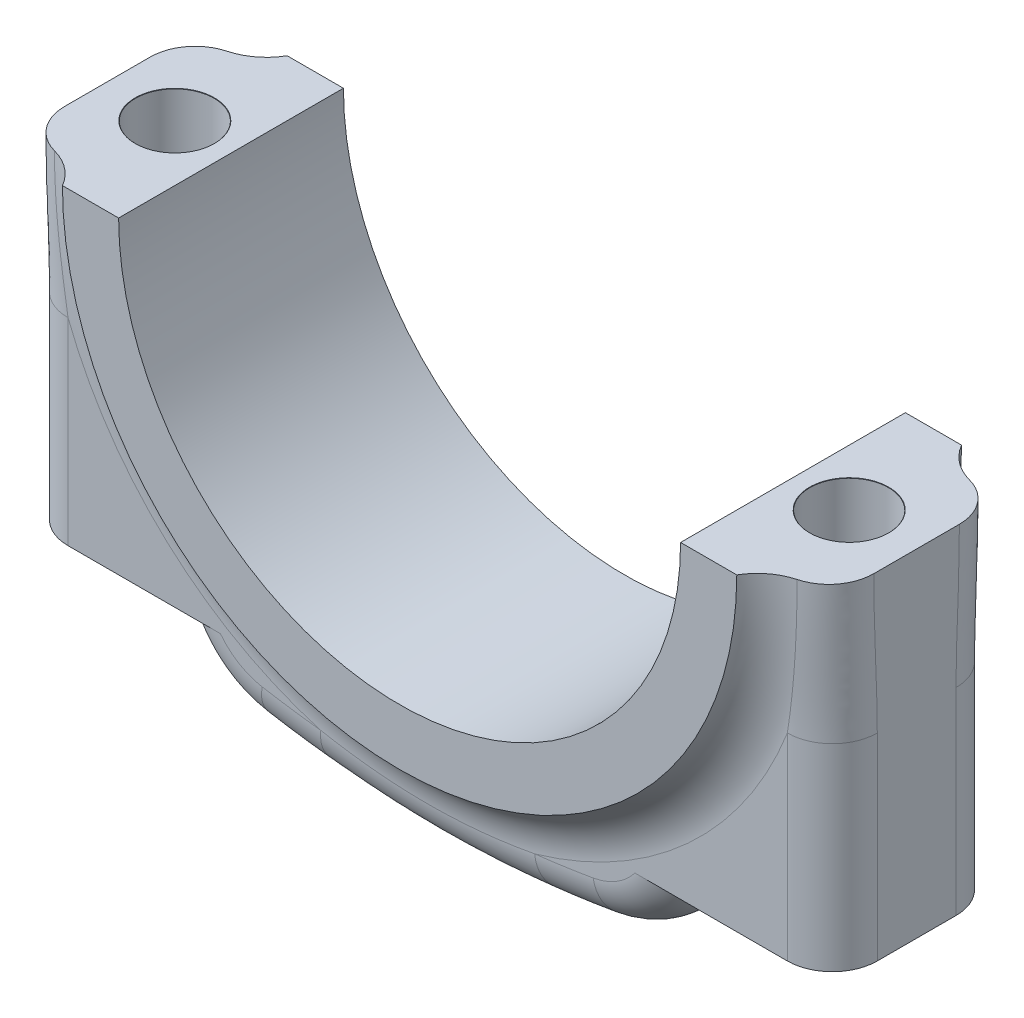
SolidWorks part; units mm, degrees
material "1060 Alloy"
ref_plane "Ebene vorne" through (0, 0, 0) normal (0, 0, 1) x (1, 0, 0)
ref_plane "Ebene oben" through (0, 0, 0) normal (0, 1, 0) x (1, 0, 0)
ref_plane "Ebene rechts" through (0, 0, 0) normal (1, 0, 0) x (0, 0, -1)
sketch "Sketch1" plane through (0, 0, 0) normal (0, 0, 1) x (1, 0, 0)
  line L0 (-36, 0) -> (-25, 0)
  line L1 (36, 0) -> (36, -30)
  line L2 (0, 49.3869) -> (0, -64.5829) construction
  line L3 (-36, 0) -> (-36, -30)
  line L4 (25, 0) -> (36, 0)
  arc A0 (-25, 0) -> (25, 0) centre (0, 0) ccw
  arc A1 (-36, -30) -> (36, -30) centre (0, 52.4864) ccw
  dimension "D3" = 50
  dimension "D4" = 180
  dimension "D1" = 36
  dimension "D2" = 30
extrude "Boss-Extrude1" add sketch "Sketch1" along normal mid plane 15
sketch "Sketch2" plane through (0, 0, 7.5) normal (0, 0, 1) x (1, 0, 0)
  line L0 (-30, 0) -> (-25, 0)
  line L1 (25, 0) -> (30, 0)
  arc A0 (-25, 0) -> (25, 0) centre (0, 0) ccw construction
  arc A1 (-25, 0) -> (25, 0) centre (0, 0) ccw
  arc A2 (-30, 0) -> (30, 0) centre (0, 0) ccw
  dimension "D1" = 60
extrude "Boss-Extrude2" add sketch "Sketch2" along normal blind 2.5
sketch "Sketch3" plane through (0, 0, -7.5) normal (0, 0, -1) x (-1, 0, 0)
  line L2 (30, 0) -> (25, 0)
  line L3 (-25, 0) -> (-30, 0)
  line L4 (30, 0) -> (25, 0)
  line L5 (-25, 0) -> (-30, 0)
  arc A2 (-25, 0) -> (25, 0) centre (0, 0) ccw
  arc A3 (-30, 0) -> (30, 0) centre (0, 0) ccw
  arc A4 (-25, 0) -> (25, 0) centre (0, 0) ccw
  arc A5 (-30, 0) -> (30, 0) centre (0, 0) ccw
  dimension "D1" = 0
extrude "Boss-Extrude3" add sketch "Sketch3" along normal blind 2.5
fillet "Fillet1" radius 5 2 edges at (0, -30, -7.5) (0, -30, 7.5)
hole_wizard "Ø7.0 (7) Diameter Hole5" positions "Sketch4" profile "Sketch5" hole size "Ø7.0" standard "ISO" end condition through all
sketch "Sketch4" plane through (0, 0, 0) normal (0, 1, 0) x (1, 0, 0)
  line L0 (0, 0) -> (0, 15.0556) construction
  point P0 (30, 0)
  point P2 (-30, 0)
  dimension "D1" = 30
sketch "Sketch5" plane through (30, 0, 0) normal (1, 0, 0) x (0, 0, 1)
  line L0 (0, 0) -> (0, 37.5136)
  line L1 (0, 37.5136) -> (3.5, 37.5136)
  line L2 (3.5, 37.5136) -> (3.5, 0.025)
  line L3 (3.5, 0.025) -> (3.525, 0)
  line L5 (3.525, 0) -> (0, 0)
  line L6 (-3.5, 0.025) -> (-3.525, 0) construction
  line L11 (0, -6.35) -> (0, 107.95) construction
  dimension "Thru Hole Dia." = 7
  dimension "Thru Hole Depth" = 37.5136
  dimension "Near C'Sink Dia." = 7.05
  dimension "Near C'Sink Angle" = 90
ref_plane "Plane1" through (0, -30, 0) normal (0, 1, 0) x (1, 0, 0)
sketch "Sketch6" plane through (0, -30, 0) normal (0, 1, 0) x (1, 0, 0)
  line L0 (0, 0.5683) -> (0, -22.8934) construction
  line L1 (23, -13.2327) -> (43.5392, -13.2327)
  line L2 (23, -13.2327) -> (23, 16.1553)
  line L3 (23, 16.1553) -> (43.5392, 16.1553)
  line L4 (43.5392, -13.2327) -> (43.5392, 16.1553)
  line L5 (-23, 16.1553) -> (-43.5392, 16.1553)
  line L6 (-43.5392, -13.2327) -> (-43.5392, 16.1553)
  line L7 (-23, -13.2327) -> (-43.5392, -13.2327)
  line L8 (-23, -13.2327) -> (-23, 16.1553)
  dimension "D1" = 29.388
  dimension "D2" = 23
extrude "Cut-Extrude1" cut sketch "Sketch6" against normal through all
fillet "Fillet2" radius 10 2 edges at (-23, -34.5251, 0) (23, -34.5251, 0)
fillet "Fillet3" radius 4 10 edges at (-20.0132, -34.085, 7.5) (0, -37.5136, 7.5) (20.0132, -34.085, -7.5) (0, -37.5136, -7.5) (-36, -15, 7.5) (-36, -15, -7.5) (36, -15, -7.5) (36, -15, 7.5) (20.0132, -34.085, 7.5) (-20.0132, -34.085, -7.5)
